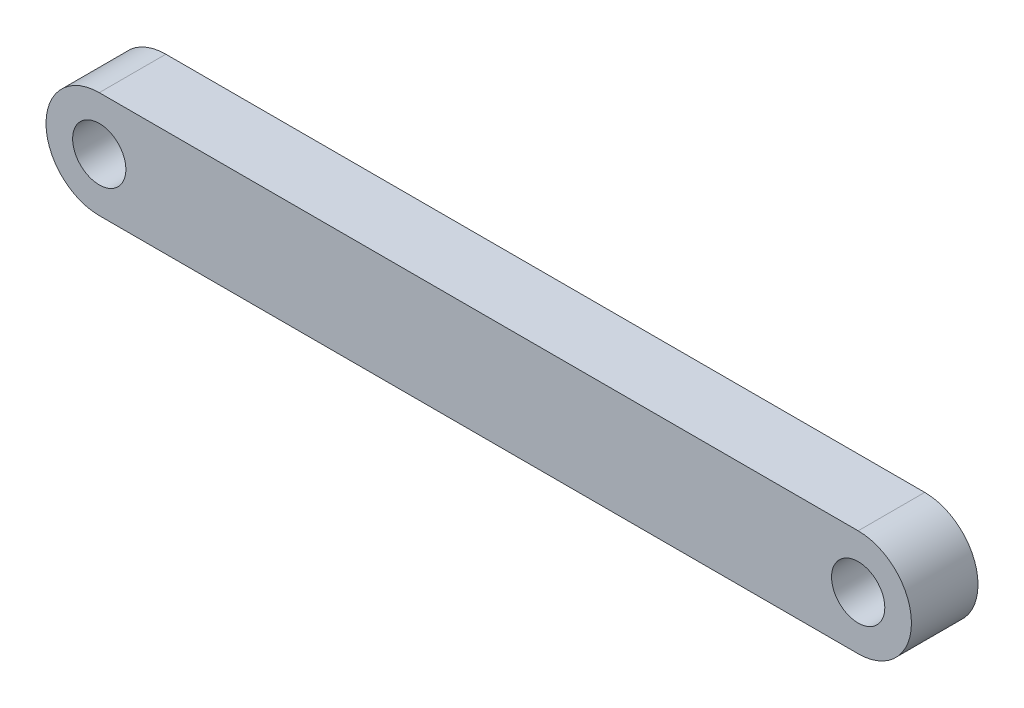
SolidWorks part; units mm, degrees
material "ABS"
ref_plane "Front Plane" through (0, 0, 0) normal (0, 0, 1) x (1, 0, 0)
ref_plane "Top Plane" through (0, 0, 0) normal (0, 1, 0) x (1, 0, 0)
ref_plane "Right Plane" through (0, 0, 0) normal (1, 0, 0) x (0, 0, -1)
sketch "Sketch1" plane through (0, 0, 0) normal (0, 0, 1) x (1, 0, 0)
  line L0 (0, 0) -> (57, 0) construction
  line L1 (0, 4) -> (57, 4)
  line L2 (0, -4) -> (57, -4)
  arc A0 (0, 4) -> (0, -4) centre (0, 0) ccw
  arc A1 (57, -4) -> (57, 4) centre (57, 0) ccw
  point P3 (28.5, 0)
  dimension "D2" = 4
  dimension "D1" = 57
extrude "Boss-Extrude1" add sketch "Sketch1" along normal mid plane 5
sketch "Sketch2" plane through (0, 0, 2.5) normal (0, 0, 1) x (1, 0, 0)
  circle A0 centre (57, 0) radius 2
  circle A1 centre (0, 0) radius 2
  dimension "D1" = 4
  dimension "D2" = 4
extrude "Cut-Extrude1" cut sketch "Sketch2" against normal through all
